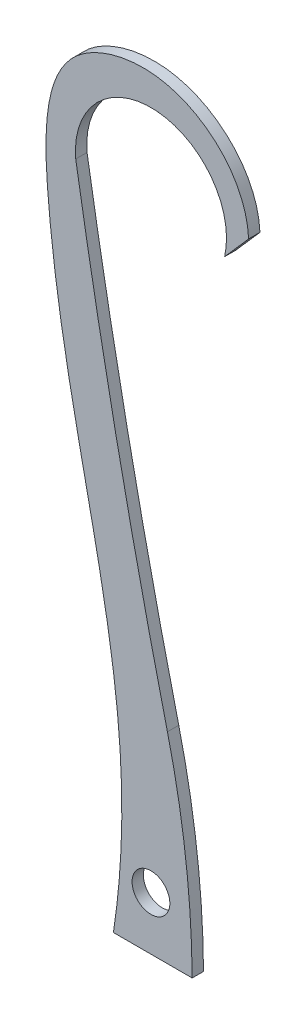
SolidWorks part; units mm, degrees
ref_plane "Front Plane" through (0, 0, 0) normal (0, 0, 1) x (1, 0, 0)
ref_plane "Top Plane" through (0, 0, 0) normal (0, 1, 0) x (1, 0, 0)
ref_plane "Right Plane" through (0, 0, 0) normal (1, 0, 0) x (0, 0, -1)
sketch "Sketch2" plane through (0, 0, 0) normal (0, 0, 1) x (1, 0, 0)
  line L0 (-50.8, 0) -> (65.5397, 0) construction
  line L1 (-50.8, 0) -> (-50.8, -1091.1785) construction
  line L2 (-1.2748, -11.309) -> (14.8715, 7.1008)
  line L3 (-76.0421, -442.2926) -> (-23.0882, -442.2926)
  line L4 (-23.0882, -373.3488) -> (-23.0882, -442.2926)
  arc A0 (-101.6, 0) -> (-1.2748, -11.309) centre (-50.8, 0) cw
  circle A1 centre (-50.8, 0) radius 50.8 construction
  arc A2 (-101.6, 0) -> (-101.402, -4.4814) centre (-50.8, 0) ccw
  circle A3 centre (-50.8, -406.4) radius 12.7
  spline S0 degree 3 poles (14.8715, 7.1008) (13.3753, 41.3113) (-33.0888, 83.5528) (-124.3959, 55.9187) (-118.6924, -164.8605) (-53.163, -292.7379) (-76.0421, -442.2926) knots 0 0 0 0 0.14957 0.231036 0.376411 1 1 1 1
  spline S1 degree 2 poles (-101.402, -4.4814) (-70.6769, -190.6401) (-23.0882, -373.3488) knots 0 0 0 1 1 1
  point P2 (-119.7418, -38.1476)
  point P8 (-101.6, 55.1631)
  point P16 (-50.8, 71.192)
  point P22 (0, 44.8589)
  dimension "D1" = 50.8
  dimension "D2" = 25.4
  dimension "D3" = 406.4
extrude "Boss-Extrude1" add sketch "Sketch2" along normal blind 7.62
fillet "Fillet1" radius 589.28 1 edges at (-23.0882, -373.3488, 3.81)
